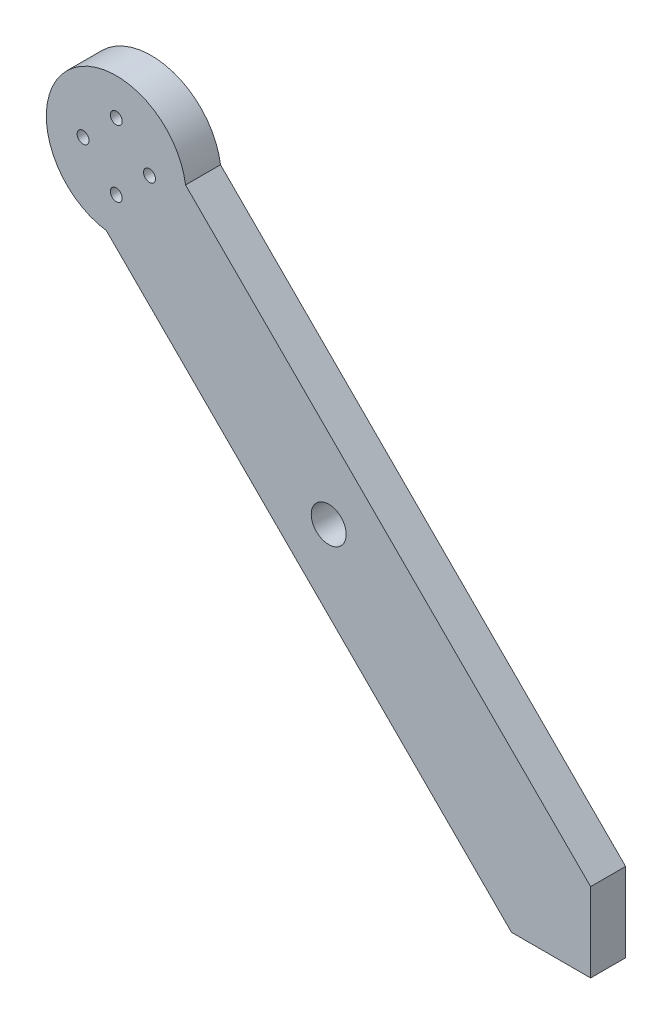
SolidWorks part; units mm, degrees
ref_plane "Plan de face" through (0, 0, 0) normal (0, 0, 1) x (1, 0, 0)
ref_plane "Plan de dessus" through (0, 0, 0) normal (0, 1, 0) x (1, 0, 0)
ref_plane "Plan de droite" through (0, 0, 0) normal (1, 0, 0) x (0, 0, -1)
sketch "Esquisse1" plane through (0, 0, 0) normal (0, 0, 1) x (1, 0, 0)
  line L0 (-22.6274, 0) -> (0, 0)
  line L1 (0, 0) -> (0, 22.6274)
  line L2 (32.3726, 55) -> (0, 22.6274) construction
  line L3 (0, 22.6274) -> (-32.3726, 55)
  line L4 (-32.3726, 55) -> (-124.2965, 146.9239)
  line L5 (-124.2965, 146.9239) -> (-146.9239, 124.2965)
  line L6 (-146.9239, 124.2965) -> (-55, 32.3726)
  line L7 (-55, 32.3726) -> (-22.6274, 0)
  line L8 (-32.3726, 55) -> (-55, 32.3726) construction
  circle A0 centre (-135.6102, 135.6102) radius 20
  dimension "D2" = 40
  dimension "D1" = 130
extrude "Boss.-Extru.1" add sketch "Esquisse1" along normal blind 10 contours A0 L6 L7 L0 L1 L3 L4 | L6 A0 L4 L5 | L4 A0 L6 L5 region at (-64.3798, 64.3798, 0) region at (-140.742, 140.742, 0) region at (-129.2859, 129.2859, 0)
sketch "Esquisse2" plane through (0, 0, 0) normal (0, 0, -1) x (-1, 0, 0)
  circle A1 centre (31.8198, 31.8198) radius 5 construction
  circle A2 centre (14.1421, 14.1421) radius 5 construction
  circle A3 centre (31.8198, 31.8198) radius 5
  circle A4 centre (14.1421, 14.1421) radius 5
extrude "Boss.-Extru.2" add sketch "Esquisse2" along normal up to surface (5 mm away)
sketch "Esquisse3" plane through (0, 0, 0) normal (0, 0, -1) x (-1, 0, 0)
  line L0 (135.6102, 135.6102) -> (149.7523, 149.7523) construction
  line L1 (135.6102, 135.6102) -> (135.6102, 145.1102) construction
  line L2 (135.6102, 135.6102) -> (135.6102, 145.1102) construction
  line L3 (135.6102, 135.6102) -> (145.1102, 135.6102) construction
  line L4 (0, 0) -> (149.7523, 149.7523) construction
  circle A0 centre (135.6102, 135.6102) radius 9.5 construction
  arc A1 (138.4386, 115.8112) -> (115.8112, 138.4386) centre (135.6102, 135.6102) ccw construction
  circle A2 centre (135.6102, 145.1102) radius 1.7
  circle A3 centre (145.1102, 135.6102) radius 1.7
  circle A4 centre (135.6102, 126.1102) radius 1.7
  circle A5 centre (126.1102, 135.6102) radius 1.7
  circle A6 centre (74.8762, 74.8762) radius 5
  point P7 (0, 0)
  point P20 (0, 0)
  point P21 (0, 0)
  point P23 (148.128, 148.128)
  dimension "D1" = 19
  dimension "D3" = 3.4
  dimension "D6" = 10
  dimension "D2" = 45
  dimension "D5" = 90
  dimension "D4" = 4
extrude "Enlèv. mat.-Extru.1" cut sketch "Esquisse3" against normal through all
